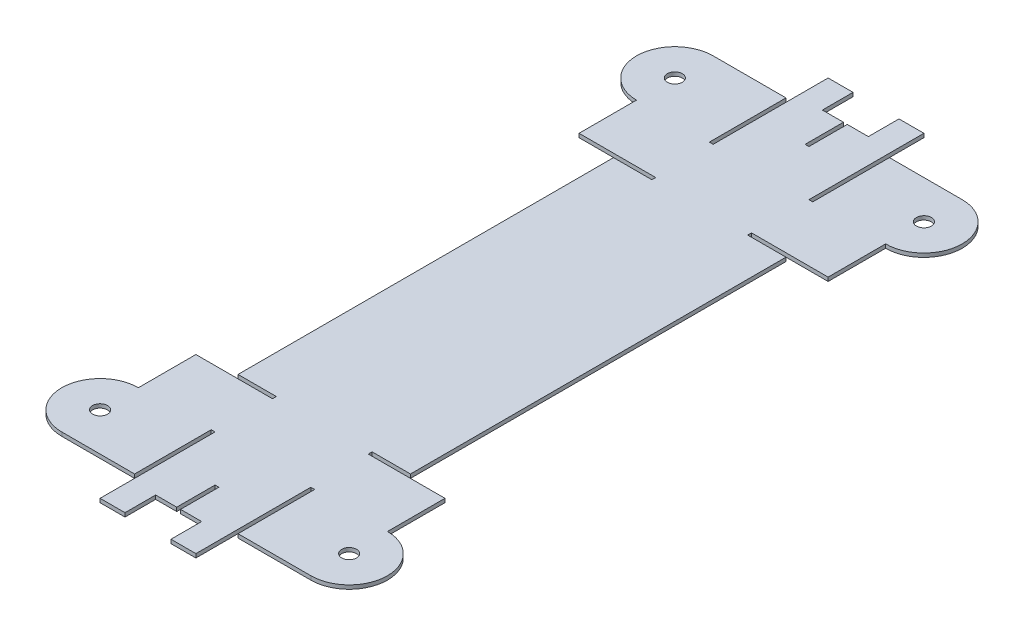
SolidWorks part; units mm, degrees
ref_plane "Front Plane" through (0, 0, 0) normal (0, 0, 1) x (1, 0, 0)
ref_plane "Top Plane" through (0, 0, 0) normal (0, 1, 0) x (1, 0, 0)
ref_plane "Right Plane" through (0, 0, 0) normal (1, 0, 0) x (0, 0, -1)
sketch "Sketch1" plane through (0, 0, 0) normal (0, 1, 0) x (1, 0, 0)
  line L0 (-32.5, 85) -> (-13.5, 85)
  line L1 (-12.5, 95) -> (12.5, 95) construction
  line L2 (-12.5, 95) -> (-12.5, -95) construction
  line L3 (-12.5, -95) -> (12.5, -95) construction
  line L4 (12.5, 95) -> (12.5, -95) construction
  line L5 (-12.5, 95) -> (12.5, -95) construction
  line L6 (-12.5, -95) -> (12.5, 95) construction
  line L7 (32.5, -75) -> (-32.5, -75) construction
  line L8 (32.5, -75) -> (32.5, 75) construction
  line L9 (32.5, 75) -> (-32.5, 75) construction
  line L10 (-32.5, -75) -> (-32.5, 75) construction
  line L11 (32.5, -75) -> (-32.5, 75) construction
  line L12 (32.5, 75) -> (-32.5, -75) construction
  line L13 (-13.5, 85) -> (-13.5, 65)
  line L14 (-13.5, 65) -> (-12.5, 65)
  line L15 (-12.5, 65) -> (-12.5, 95)
  line L16 (-12.5, 95) -> (-6, 95)
  line L17 (-6, 95) -> (-6, 87)
  line L18 (-6, 87) -> (-0.5, 87)
  line L19 (6, 87) -> (6, 95)
  line L20 (6, 95) -> (12.5, 95)
  line L21 (0, 95) -> (0, 87) construction
  line L22 (-0.5, 87) -> (-0.5, 77)
  line L23 (-0.5, 77) -> (0.5, 77)
  line L24 (0.5, 77) -> (0.5, 87)
  line L25 (0, 77) -> (0, 87) construction
  line L26 (0.5, 87) -> (6, 87)
  line L27 (-0.5, 87) -> (0, 87) construction
  line L28 (0, 87) -> (0.5, 87) construction
  line L29 (0, 0) -> (12.5, 0) construction
  line L30 (-32.5, 65) -> (-32.5, 50)
  line L31 (-32.5, 50) -> (-12.5, 50)
  line L32 (-12.5, 50) -> (-12.5, 49)
  line L33 (-12.5, 49) -> (-22.5, 49)
  line L34 (-22.5, 49) -> (-22.5, -49)
  line L35 (-22.5, 0) -> (-12.5, 0) construction
  line L36 (12.5, 65) -> (12.5, 95)
  line L37 (13.5, 65) -> (12.5, 65)
  line L38 (13.5, 85) -> (13.5, 65)
  line L39 (32.5, 85) -> (13.5, 85)
  line L40 (32.5, 65) -> (32.5, 50)
  line L41 (32.5, 50) -> (12.5, 50)
  line L42 (12.5, 50) -> (12.5, 49)
  line L43 (12.5, 49) -> (22.5, 49)
  line L44 (22.5, 49) -> (22.5, -49)
  line L45 (22.5, 0) -> (12.5, 0) construction
  line L46 (12.5, -49) -> (22.5, -49)
  line L47 (12.5, -50) -> (12.5, -49)
  line L48 (32.5, -50) -> (12.5, -50)
  line L49 (32.5, -65) -> (32.5, -50)
  line L50 (32.5, -85) -> (13.5, -85)
  line L51 (13.5, -85) -> (13.5, -65)
  line L52 (13.5, -65) -> (12.5, -65)
  line L53 (12.5, -65) -> (12.5, -95)
  line L54 (6, -95) -> (12.5, -95)
  line L55 (6, -87) -> (6, -95)
  line L56 (0.5, -87) -> (6, -87)
  line L57 (0.5, -77) -> (0.5, -87)
  line L58 (-0.5, -77) -> (0.5, -77)
  line L59 (-0.5, -87) -> (-0.5, -77)
  line L60 (-6, -87) -> (-0.5, -87)
  line L61 (-6, -95) -> (-6, -87)
  line L62 (-12.5, -95) -> (-6, -95)
  line L63 (-12.5, -65) -> (-12.5, -95)
  line L64 (-13.5, -65) -> (-12.5, -65)
  line L65 (-13.5, -85) -> (-13.5, -65)
  line L66 (-32.5, -85) -> (-13.5, -85)
  line L67 (-32.5, -65) -> (-32.5, -50)
  line L68 (-32.5, -50) -> (-12.5, -50)
  line L69 (-12.5, -50) -> (-12.5, -49)
  line L70 (-12.5, -49) -> (-22.5, -49)
  circle A0 centre (-32.5, 75) radius 1.95
  arc A1 (-32.5, 85) -> (-32.5, 65) centre (-32.5, 75) ccw
  arc A8 (-32.5, 65) -> (-32.5, 85) centre (-32.5, 75) ccw construction
  circle A9 centre (32.5, 75) radius 1.95
  arc A10 (32.5, 85) -> (32.5, 65) centre (32.5, 75) cw
  arc A11 (32.5, 65) -> (32.5, 85) centre (32.5, 75) cw construction
  circle A12 centre (32.5, -75) radius 1.95
  arc A13 (32.5, -65) -> (32.5, -85) centre (32.5, -75) ccw construction
  arc A14 (32.5, -85) -> (32.5, -65) centre (32.5, -75) ccw
  circle A15 centre (-32.5, -75) radius 1.95
  arc A16 (-32.5, -85) -> (-32.5, -65) centre (-32.5, -75) cw
  arc A17 (-32.5, -65) -> (-32.5, -85) centre (-32.5, -75) cw construction
  point P0 (0, 0)
  point P18 (0, 0)
  dimension "D1" = 3.9
  dimension "D2" = 20
  dimension "D3" = 20
  dimension "D4" = 25
  dimension "D5" = 20
  dimension "D6" = 150
  dimension "D7" = 12
  dimension "D8" = 8
  dimension "D9" = 1
  dimension "D10" = 10
  dimension "D11" = 20
  dimension "D12" = 1
  dimension "D13" = 1
  dimension "D14" = 25
  dimension "D15" = 10
extrude "Boss-Extrude1" add sketch "Sketch1" along normal blind 1
